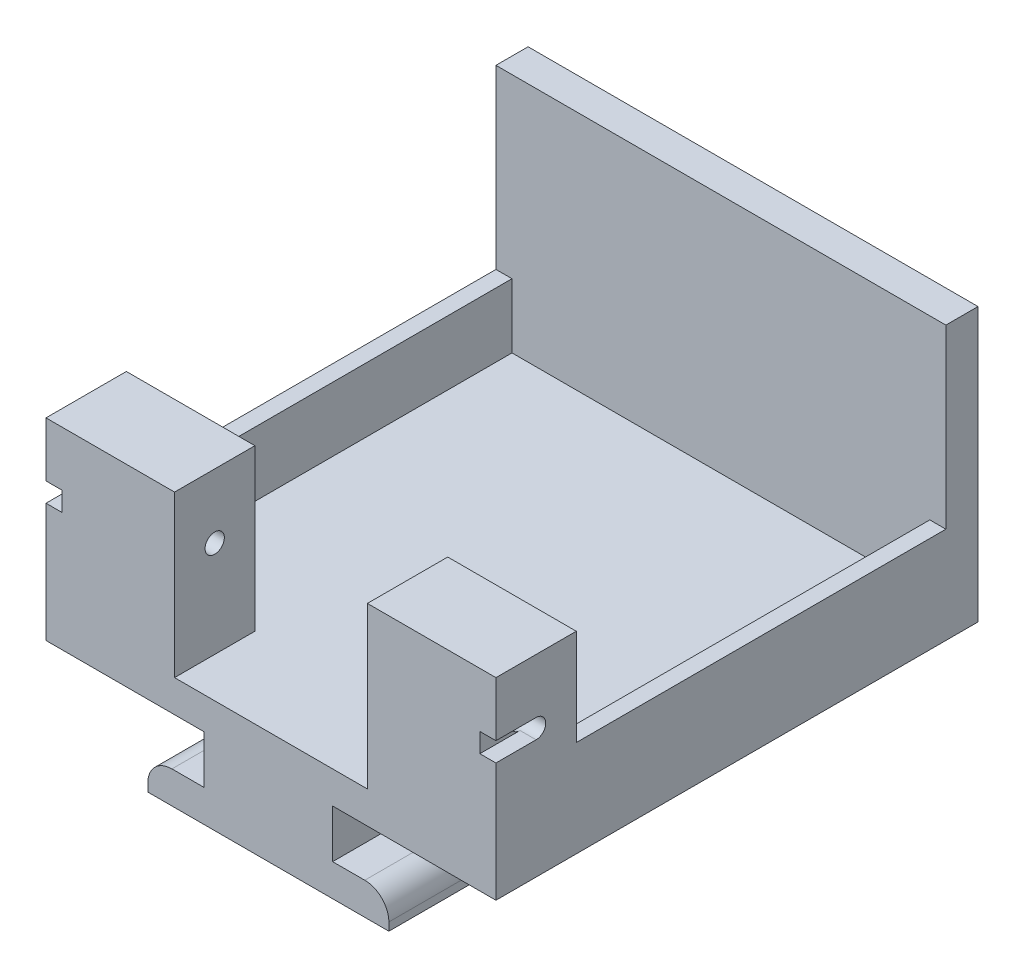
SolidWorks part; units mm, degrees
ref_plane "前视基准面" through (0, 0, 0) normal (0, 0, 1) x (1, 0, 0)
ref_plane "上视基准面" through (0, 0, 0) normal (0, 1, 0) x (1, 0, 0)
ref_plane "右视基准面" through (0, 0, 0) normal (1, 0, 0) x (0, 0, -1)
other "Configuration Table"
sketch "草图1" plane through (0, 0, 0) normal (0, 0, 1) x (1, 0, 0)
  line L0 (-13.928, -1.6693) -> (-4.0904, -1.6693)
  line L1 (-13.928, 0.3307) -> (14.072, 0.3307)
  line L2 (-13.928, 0.3307) -> (-13.928, -1.6693)
  line L3 (-7.5904, -6.6693) -> (7.4096, -6.6693)
  line L4 (14.072, 0.3307) -> (14.072, -1.6693)
  line L5 (3.9096, -1.6693) -> (14.072, -1.6693)
  line L7 (-4.0904, -1.6693) -> (-4.0904, -4.6693)
  line L9 (3.9096, -1.6693) -> (3.9096, -4.6693)
  line L10 (-4.0904, -4.6693) -> (-7.5904, -4.6693)
  line L11 (7.4096, -4.6693) -> (3.9096, -4.6693)
  line L12 (7.4096, -4.6693) -> (7.4096, -6.6693)
  line L14 (-7.5904, -4.6693) -> (-7.5904, -6.6693)
  dimension "D1" = 28
  dimension "D2" = 2
  dimension "D3" = 8
  dimension "D4" = 3
  dimension "D5" = 2
  dimension "D6" = 15
extrude "凸台-拉伸1" add sketch "草图1" along normal blind 30
fillet "圆角1" radius 1.5 2 edges at (-7.5904, -4.6693, 15) (7.4096, -4.6693, 15)
sketch "草图2" plane through (0, 0.3307, 0) normal (0, 1, 0) x (1, 0, 0)
  line L0 (0, 0) -> (0.072, -30) construction
  line L1 (14.072, -30) -> (-13.928, -30) construction
  line L2 (-13.928, -30) -> (-13.928, 0) construction
  line L3 (-13.928, -25) -> (-5.928, -25)
  line L4 (-13.928, -25) -> (-13.928, -30)
  line L5 (-13.928, -30) -> (-5.928, -30)
  line L6 (-5.928, -25) -> (-5.928, -30)
  line L12 (14.072, -30) -> (6.072, -30)
  line L13 (14.072, -30) -> (14.072, -25)
  line L14 (14.072, -25) -> (6.072, -25)
  line L15 (6.072, -30) -> (6.072, -25)
  dimension "D1" = 5
  dimension "D2" = 8
  dimension "D3" = 5
  dimension "D4" = 8
extrude "凸台-拉伸2" add sketch "草图2" along normal blind 10
sketch "草图3" plane through (-13.928, 0, 0) normal (-1, 0, 0) x (0, 0, 1)
  line L0 (27.5, 10.3307) -> (27.5, -1.6693) construction
  line L1 (25, 10.3307) -> (30, 10.3307) construction
  line L2 (30, -1.6693) -> (0, -1.6693) construction
  circle A0 centre (27.5, 6.3307) radius 0.6
  dimension "D2" = 1.2
  dimension "D1" = 4
extrude "切除-拉伸1" cut sketch "草图3" against normal through all
sketch "草图4" plane through (0, 0.3307, 0) normal (0, 1, 0) x (1, 0, 0)
  line L0 (14.072, -25) -> (14.072, 0) construction
  line L1 (-13.928, 0) -> (14.072, 0)
  line L2 (-13.928, 0) -> (-13.928, -2)
  line L3 (-13.928, -2) -> (14.072, -2)
  line L4 (14.072, 0) -> (14.072, -2)
  line L10 (14.072, -25) -> (6.072, -25) construction
  line L11 (14.072, -2) -> (13.072, -2)
  line L12 (14.072, -2) -> (14.072, -25)
  line L13 (14.072, -25) -> (13.072, -25)
  line M12 (14.072, -25) -> (14.072, 0)
  line M13 (14.072, 0) -> (-13.928, 0)
  line M14 (-13.928, 0) -> (-13.928, -25)
  dimension "D1" = 2
  dimension "D2" = 1
extrude "凸台-拉伸4" add sketch "草图4" along normal blind 15 contours L3 M14 M12 M13 region at (0.072, 0.3307, 1)
sketch "草图6" plane through (0, 0.3307, 0) normal (0, 1, 0) x (1, 0, 0)
  line L0 (-5.928, -25) -> (-13.928, -25) construction
  line L1 (-13.928, -2) -> (-12.928, -2)
  line L2 (-13.928, -2) -> (-13.928, -25)
  line L3 (-13.928, -25) -> (-12.928, -25)
  line L4 (-12.928, -2) -> (-12.928, -25)
  line L5 (14.072, -25) -> (6.072, -25) construction
  line L6 (14.072, -2) -> (13.072, -2)
  line L7 (14.072, -2) -> (14.072, -25)
  line L8 (14.072, -25) -> (13.072, -25)
  line L9 (13.072, -2) -> (13.072, -25)
  dimension "D1" = 1
  dimension "D2" = 1
sketch "草图8" plane through (-13.928, 0, 0) normal (-1, 0, 0) x (0, 0, 1)
  line L0 (30, 10.3307) -> (30, -1.6693) construction
  line L1 (27.5, 6.9307) -> (30, 6.9307)
  line L2 (27.5, 6.9307) -> (27.5, 5.7307)
  line L3 (27.5, 5.7307) -> (30, 5.7307)
  line L4 (30, 6.9307) -> (30, 5.7307)
  circle A0 centre (27.5, 6.3307) radius 0.6 construction
extrude "切除-拉伸3" cut sketch "草图8" against normal blind 1
sketch "草图9" plane through (14.072, 0, 0) normal (1, 0, 0) x (0, 0, -1)
  line L1 (-27.5, 6.9307) -> (-30, 6.9307)
  line L2 (-27.5, 6.9307) -> (-27.5, 5.7307)
  line L3 (-27.5, 5.7307) -> (-30, 5.7307)
  line L4 (-30, 6.9307) -> (-30, 5.7307)
extrude "切除-拉伸4" cut sketch "草图9" against normal blind 1
extrude "凸台-拉伸6" add sketch "草图6" along normal blind 4
